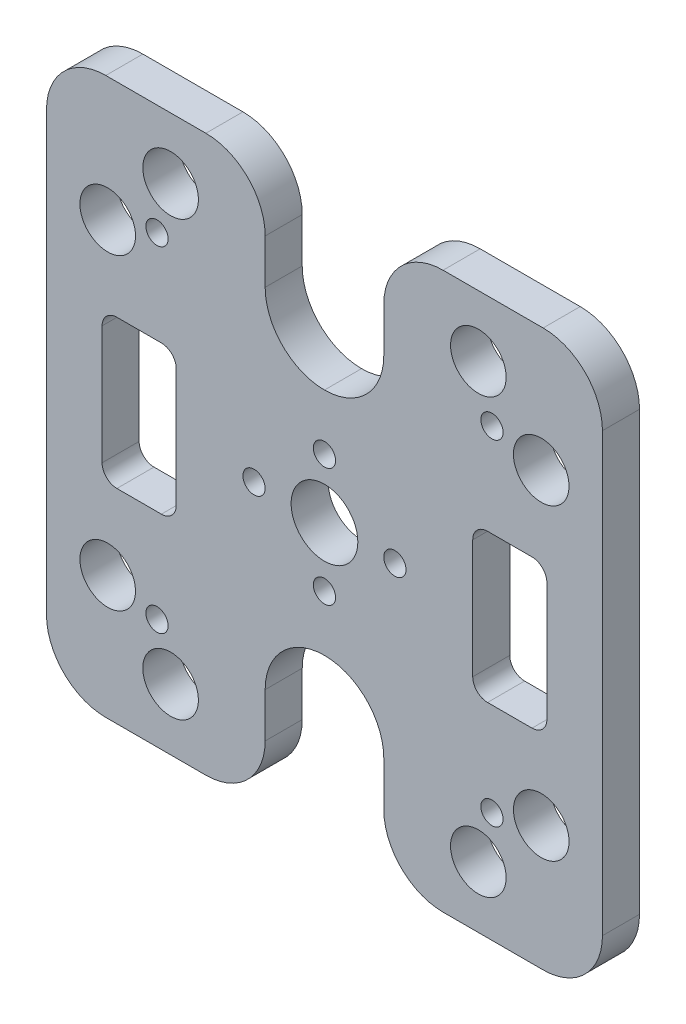
SolidWorks part; units mm, degrees
material "Balsa"
ref_plane "Front Plane" through (0, 0, 0) normal (0, 0, 1) x (1, 0, 0)
ref_plane "Top Plane" through (0, 0, 0) normal (0, 1, 0) x (1, 0, 0)
ref_plane "Right Plane" through (0, 0, 0) normal (1, 0, 0) x (0, 0, -1)
sketch "Sketch1" plane through (0, 0, 0) normal (0, 0, 1) x (-1, 0, 0)
  line L0 (0, 8) -> (0, -8) construction
  line L1 (9.5, 0) -> (-9.5, 0) construction
  line L2 (29.2426, 20.7574) -> (20.7574, 29.2426) construction
  line L3 (37.5, -37.5) -> (-37.5, -37.5)
  line L4 (37.5, -37.5) -> (37.5, 37.5)
  line L5 (37.5, 37.5) -> (-37.5, 37.5)
  line L6 (-37.5, -37.5) -> (-37.5, 37.5)
  line L7 (37.5, -37.5) -> (-37.5, 37.5) construction
  line L8 (37.5, 37.5) -> (-37.5, -37.5) construction
  line L9 (-25, -25) -> (25, -25) construction
  line L10 (-25, -25) -> (-25, 25) construction
  line L11 (-25, 25) -> (25, 25) construction
  line L12 (25, -25) -> (25, 25) construction
  line L13 (-25, -25) -> (25, 25) construction
  line L14 (-25, 25) -> (25, -25) construction
  line L15 (-30, 10) -> (-20, 10)
  line L16 (30, -10) -> (20, -10)
  line L17 (30, -10) -> (30, 10)
  line L18 (30, 10) -> (20, 10)
  line L19 (20, -10) -> (20, 10)
  line L20 (30, -10) -> (20, 10) construction
  line L21 (30, 10) -> (20, -10) construction
  line L22 (-20, -10) -> (-20, 10)
  line L23 (-30, -10) -> (-20, -10)
  line L24 (-30, -10) -> (-30, 10)
  line L26 (22.594, -22.594) -> (-22.594, -22.594) construction
  line L27 (22.594, -22.594) -> (22.594, 22.594) construction
  line L28 (22.594, 22.594) -> (-22.594, 22.594) construction
  line L29 (-22.594, -22.594) -> (-22.594, 22.594) construction
  line L30 (22.594, -22.594) -> (-22.594, 22.594) construction
  line L31 (22.594, 22.594) -> (-22.594, -22.594) construction
  circle A0 centre (9.5, 0) radius 1.5
  circle A1 centre (-9.5, 0) radius 1.5
  circle A2 centre (0, -8) radius 1.5
  circle A3 centre (0, 8) radius 1.5
  circle A10 centre (0, 0) radius 4.5
  circle A11 centre (20.7574, 29.2426) radius 3.75
  circle A12 centre (29.2426, 20.7574) radius 3.75
  circle A13 centre (-29.2426, -20.7574) radius 3.75
  circle A14 centre (-20.7574, -29.2426) radius 3.75
  circle A15 centre (20.7574, -29.2426) radius 3.75
  circle A16 centre (29.2426, -20.7574) radius 3.75
  circle A17 centre (-20.7574, 29.2426) radius 3.75
  circle A18 centre (-29.2426, 20.7574) radius 3.75
  circle A19 centre (22.594, 22.594) radius 1.5
  circle A20 centre (-22.594, 22.594) radius 1.5
  circle A21 centre (22.594, -22.594) radius 1.5
  circle A22 centre (-22.594, -22.594) radius 1.5
  point P3 (0, 0)
  point P14 (0, 0)
  point P22 (25, 25)
  point P38 (25, 0)
  dimension "D1" = 75
  dimension "D4" = 3
  dimension "D2" = 50
extrude "Boss-Extrude1" add sketch "Sketch1" along normal blind 5
sketch "Sketch3" plane through (0, 0, 5) normal (0, 0, 1) x (1, 0, 0)
  line L0 (0, 0) -> (0, 26.5) construction
  line L1 (37.5, 37.5) -> (-37.5, 37.5) construction
  line L2 (-8, 15.5) -> (8, 15.5)
  line L3 (-8, 15.5) -> (-8, 37.5)
  line L4 (-8, 37.5) -> (8, 37.5)
  line L5 (8, 15.5) -> (8, 37.5)
  line L6 (-8, 15.5) -> (8, 37.5) construction
  line L7 (-8, 37.5) -> (8, 15.5) construction
  line L8 (0, 0) -> (-37.5, 0) construction
  line L9 (-37.5, 37.5) -> (-37.5, -37.5) construction
  line L10 (-8, -37.5) -> (8, -37.5)
  line L11 (8, -15.5) -> (8, -37.5)
  line L12 (-8, -15.5) -> (8, -15.5)
  line L13 (-8, -15.5) -> (-8, -37.5)
extrude "Cut-Extrude1" cut sketch "Sketch3" against normal up to surface (5 mm away) up to face at (-25, 0, 0)
fillet "Fillet1" radius 8 12 edges at (-37.5, -37.5, 2.5) (-8, -37.5, 2.5) (8, -15.5, 2.5) (-8, -15.5, 2.5) (8, -37.5, 2.5) (37.5, -37.5, 2.5) (37.5, 37.5, 2.5) (8, 37.5, 2.5) (8, 15.5, 2.5) (-8, 15.5, 2.5) (-8, 37.5, 2.5) (-37.5, 37.5, 2.5)
fillet "Fillet2" radius 2 8 edges at (-30, 10, 2.5) (-20, 10, 2.5) (30, 10, 2.5) (20, 10, 2.5) (30, -10, 2.5) (20, -10, 2.5) (-30, -10, 2.5) (-20, -10, 2.5)
